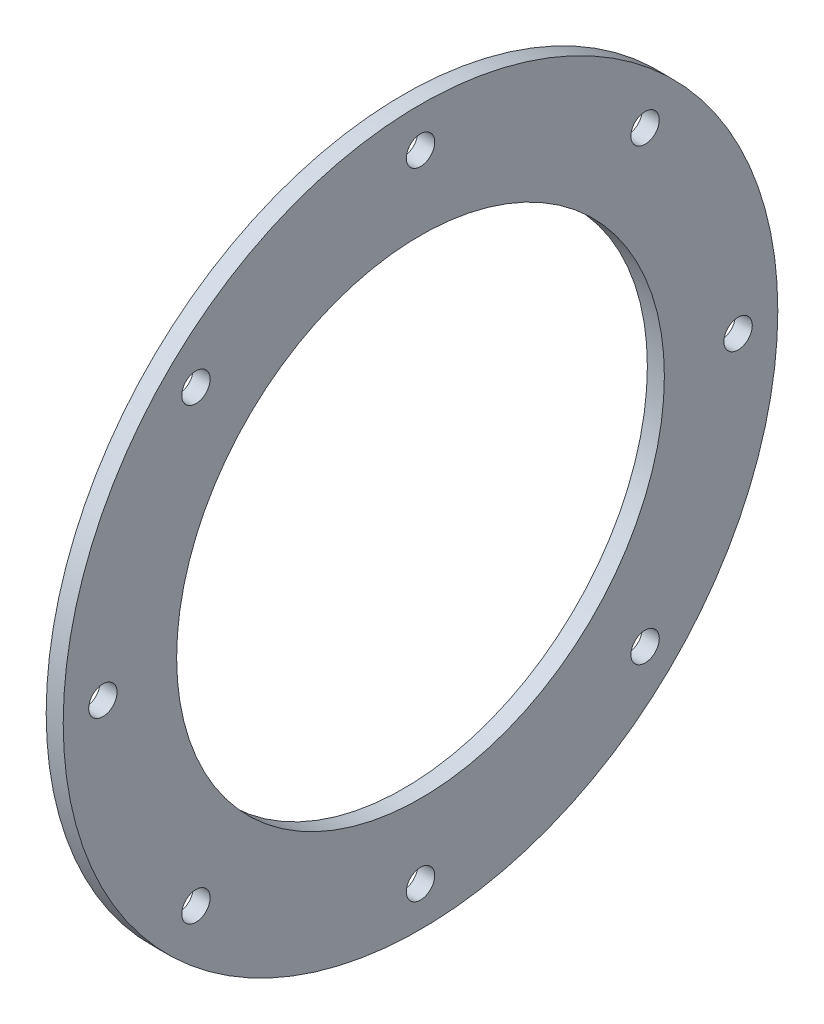
SolidWorks part; units mm, degrees
material "201 Stal nierdzewna odprężona (SS)"
ref_plane "Płaszczyzna przednia" through (0, 0, 0) normal (0, 0, 1) x (1, 0, 0)
ref_plane "Płaszczyzna górna" through (0, 0, 0) normal (0, 1, 0) x (1, 0, 0)
ref_plane "Płaszczyzna prawa" through (0, 0, 0) normal (1, 0, 0) x (0, 0, -1)
sketch "Szkic1" plane through (0, 0, 0) normal (1, 0, 0) x (0, 0, -1)
  circle A0 centre (0, 0) radius 43
  circle A1 centre (0, 0) radius 63
  circle A2 centre (0, 56) radius 2.5
  circle A3 centre (39.598, 39.598) radius 2.5
  circle A4 centre (56, 0) radius 2.5
  circle A5 centre (39.598, -39.598) radius 2.5
  circle A6 centre (0, -56) radius 2.5
  circle A7 centre (-39.598, -39.598) radius 2.5
  circle A8 centre (-56, 0) radius 2.5
  circle A9 centre (-39.598, 39.598) radius 2.5
  point P22 (0, 0)
  dimension "D1" = 86
  dimension "D2" = 126
  dimension "D3" = 5
  dimension "D4" = 56
  dimension "D5" = 8
extrude "Dodanie-wyciągnięcie1" add sketch "Szkic1" along normal blind 3
